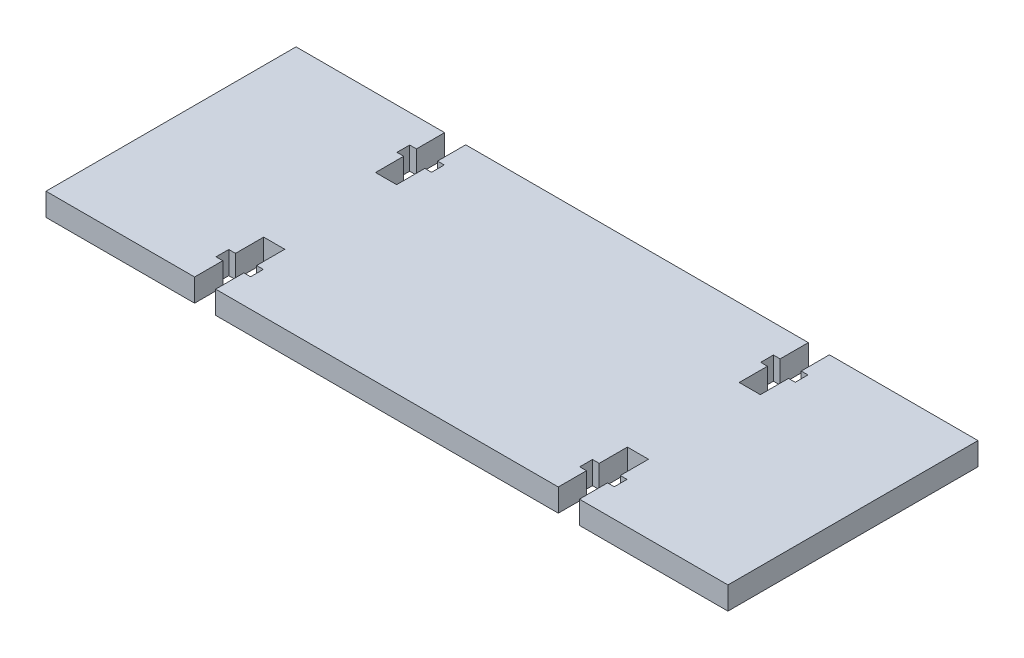
SolidWorks part; units mm, degrees
ref_plane "Front Plane" through (0, 0, 0) normal (0, 0, 1) x (1, 0, 0)
ref_plane "Top Plane" through (0, 0, 0) normal (0, 1, 0) x (1, 0, 0)
ref_plane "Right Plane" through (0, 0, 0) normal (1, 0, 0) x (0, 0, -1)
sketch "Sketch1" plane through (0, 0, 0) normal (0, 1, 0) x (1, 0, 0)
  line L1 (-47.625, -17.4625) -> (47.625, -17.4625)
  line L2 (-47.625, -17.4625) -> (-47.625, 17.4625)
  line L3 (-47.625, 17.4625) -> (47.625, 17.4625)
  line L4 (47.625, -17.4625) -> (47.625, 17.4625)
  line L5 (-47.625, -17.4625) -> (47.625, 17.4625) construction
  line L6 (-47.625, 17.4625) -> (47.625, -17.4625) construction
  point P0 (0, 0)
  dimension "D1" = 95.25
  dimension "D2" = 34.925
extrude "Boss-Extrude1" add sketch "Sketch1" along normal blind 3.175
sketch "Sketch2" plane through (0, 3.175, 0) normal (0, 1, 0) x (1, 0, 0)
  line L0 (-47.625, 17.4625) -> (-47.625, -17.4625) construction
  line L1 (-47.625, 9.4107) -> (-43.688, 9.4107)
  line L2 (-47.625, 9.4107) -> (-47.625, 6.4643)
  line L3 (-47.625, 6.4643) -> (-43.688, 6.4643)
  line L4 (-37.973, 9.4107) -> (-37.973, 6.4643)
  line L5 (-47.625, 9.4107) -> (-37.973, 6.4643) construction
  line L6 (-47.625, 7.9375) -> (-37.973, 7.9375) construction
  line L7 (47.625, 17.4625) -> (-47.625, 17.4625) construction
  line L8 (0, 0) -> (0, 17.4625) construction
  line L9 (-43.688, 5.5245) -> (-41.91, 5.5245)
  line L10 (-43.688, 5.5245) -> (-43.688, 6.4643)
  line L11 (-43.688, 10.3505) -> (-41.91, 10.3505)
  line L12 (-41.91, 5.5245) -> (-41.91, 6.4643)
  line L13 (-43.688, 5.5245) -> (-41.91, 10.3505) construction
  line L14 (-43.688, 10.3505) -> (-41.91, 5.5245) construction
  line L15 (-43.688, 9.4107) -> (-43.688, 10.3505)
  line L16 (-41.91, 6.4643) -> (-37.973, 6.4643)
  line L17 (-41.91, 9.4107) -> (-41.91, 10.3505)
  line L18 (-41.91, 9.4107) -> (-37.973, 9.4107)
  line L19 (-47.625, -6.4643) -> (-43.688, -6.4643)
  line L20 (-47.625, -6.4643) -> (-47.625, -9.4107)
  line L21 (-47.625, -9.4107) -> (-43.688, -9.4107)
  line L22 (-37.973, -6.4643) -> (-37.973, -9.4107)
  line L23 (-43.688, -10.3505) -> (-41.91, -10.3505)
  line L24 (-43.688, -10.3505) -> (-43.688, -9.4107)
  line L25 (-43.688, -5.5245) -> (-41.91, -5.5245)
  line L26 (-41.91, -10.3505) -> (-41.91, -9.4107)
  line L27 (-43.688, -6.4643) -> (-43.688, -5.5245)
  line L28 (-41.91, -9.4107) -> (-37.973, -9.4107)
  line L29 (-41.91, -6.4643) -> (-41.91, -5.5245)
  line L30 (-41.91, -6.4643) -> (-37.973, -6.4643)
  line L31 (-47.625, -6.4643) -> (-37.973, -9.4107) construction
  line L32 (-47.625, -7.9375) -> (-37.973, -7.9375) construction
  line L33 (-43.688, -10.3505) -> (-41.91, -5.5245) construction
  line L34 (-43.688, -5.5245) -> (-41.91, -10.3505) construction
  line L35 (43.688, -5.5245) -> (41.91, -10.3505) construction
  line L36 (43.688, -10.3505) -> (41.91, -5.5245) construction
  line L37 (47.625, -7.9375) -> (37.973, -7.9375) construction
  line L38 (47.625, -6.4643) -> (37.973, -9.4107) construction
  line L39 (43.688, 10.3505) -> (41.91, 5.5245) construction
  line L40 (43.688, 5.5245) -> (41.91, 10.3505) construction
  line L41 (47.625, 7.9375) -> (37.973, 7.9375) construction
  line L42 (47.625, 9.4107) -> (37.973, 6.4643) construction
  line L43 (41.91, -6.4643) -> (37.973, -6.4643)
  line L44 (41.91, -6.4643) -> (41.91, -5.5245)
  line L45 (41.91, -9.4107) -> (37.973, -9.4107)
  line L46 (43.688, -6.4643) -> (43.688, -5.5245)
  line L47 (41.91, -10.3505) -> (41.91, -9.4107)
  line L48 (43.688, -5.5245) -> (41.91, -5.5245)
  line L49 (43.688, -10.3505) -> (43.688, -9.4107)
  line L50 (43.688, -10.3505) -> (41.91, -10.3505)
  line L51 (37.973, -6.4643) -> (37.973, -9.4107)
  line L52 (47.625, -9.4107) -> (43.688, -9.4107)
  line L53 (47.625, -6.4643) -> (47.625, -9.4107)
  line L54 (47.625, -6.4643) -> (43.688, -6.4643)
  line L55 (41.91, 9.4107) -> (37.973, 9.4107)
  line L56 (41.91, 9.4107) -> (41.91, 10.3505)
  line L57 (41.91, 6.4643) -> (37.973, 6.4643)
  line L58 (43.688, 9.4107) -> (43.688, 10.3505)
  line L59 (41.91, 5.5245) -> (41.91, 6.4643)
  line L60 (43.688, 10.3505) -> (41.91, 10.3505)
  line L61 (43.688, 5.5245) -> (43.688, 6.4643)
  line L62 (43.688, 5.5245) -> (41.91, 5.5245)
  line L63 (37.973, 9.4107) -> (37.973, 6.4643)
  line L64 (47.625, 6.4643) -> (43.688, 6.4643)
  line L65 (47.625, 9.4107) -> (47.625, 6.4643)
  line L66 (47.625, 9.4107) -> (43.688, 9.4107)
  point P10 (-42.799, 7.9375)
  point P30 (-42.799, -7.9375)
  point P65 (42.799, -7.9375)
  point P66 (42.799, 7.9375)
  dimension "D1" = 9.525
  dimension "D2" = 2.9464
  dimension "D3" = 9.652
  dimension "D4" = 1.778
  dimension "D5" = 4.826
  dimension "D6" = 2
extrude "Cut-Extrude1" [suppressed] cut sketch "Sketch2" against normal through all
sketch "Sketch3" plane through (0, 3.175, 0) normal (0, 1, 0) x (1, 0, 0)
  line L0 (47.625, 17.4625) -> (-47.625, 17.4625) construction
  line L1 (-26.8732, 17.4625) -> (-23.9268, 17.4625)
  line L2 (-26.8732, 17.4625) -> (-26.8732, 13.5255)
  line L3 (-26.8732, 7.8105) -> (-23.9268, 7.8105)
  line L4 (-23.9268, 17.4625) -> (-23.9268, 13.5255)
  line L5 (-26.8732, 17.4625) -> (-23.9268, 7.8105) construction
  line L6 (-25.4, 17.4625) -> (-25.4, 7.8105) construction
  line L7 (0, -17.4625) -> (0, 17.4625) construction
  line L8 (-22.987, 13.5255) -> (-23.9268, 13.5255)
  line L9 (-22.987, 13.5255) -> (-22.987, 11.7475)
  line L10 (-22.987, 11.7475) -> (-23.9268, 11.7475)
  line L11 (-27.813, 13.5255) -> (-27.813, 11.7475)
  line L12 (-22.987, 13.5255) -> (-27.813, 11.7475) construction
  line L13 (-22.987, 11.7475) -> (-27.813, 13.5255) construction
  line L14 (0, 0) -> (-47.625, 0) construction
  line L15 (-47.625, 17.4625) -> (-47.625, -17.4625) construction
  line L16 (-26.8732, 13.5255) -> (-27.813, 13.5255)
  line L17 (-26.8732, 11.7475) -> (-26.8732, 7.8105)
  line L18 (-26.8732, 11.7475) -> (-27.813, 11.7475)
  line L19 (-23.9268, 11.7475) -> (-23.9268, 7.8105)
  line L20 (23.9268, 17.4625) -> (26.8732, 17.4625)
  line L21 (23.9268, 17.4625) -> (23.9268, 13.5255)
  line L22 (23.9268, 7.8105) -> (26.8732, 7.8105)
  line L23 (26.8732, 17.4625) -> (26.8732, 13.5255)
  line L24 (27.813, 13.5255) -> (26.8732, 13.5255)
  line L25 (27.813, 13.5255) -> (27.813, 11.7475)
  line L26 (27.813, 11.7475) -> (26.8732, 11.7475)
  line L27 (22.987, 13.5255) -> (22.987, 11.7475)
  line L28 (23.9268, 13.5255) -> (22.987, 13.5255)
  line L29 (23.9268, 11.7475) -> (23.9268, 7.8105)
  line L30 (23.9268, 11.7475) -> (22.987, 11.7475)
  line L31 (26.8732, 11.7475) -> (26.8732, 7.8105)
  line L32 (23.9268, 17.4625) -> (26.8732, 7.8105) construction
  line L33 (25.4, 17.4625) -> (25.4, 7.8105) construction
  line L34 (27.813, 13.5255) -> (22.987, 11.7475) construction
  line L35 (27.813, 11.7475) -> (22.987, 13.5255) construction
  line L36 (27.813, -11.7475) -> (22.987, -13.5255) construction
  line L37 (27.813, -13.5255) -> (22.987, -11.7475) construction
  line L38 (25.4, -17.4625) -> (25.4, -7.8105) construction
  line L39 (23.9268, -17.4625) -> (26.8732, -7.8105) construction
  line L40 (-22.987, -11.7475) -> (-27.813, -13.5255) construction
  line L41 (-22.987, -13.5255) -> (-27.813, -11.7475) construction
  line L42 (-25.4, -17.4625) -> (-25.4, -7.8105) construction
  line L43 (-26.8732, -17.4625) -> (-23.9268, -7.8105) construction
  line L44 (26.8732, -11.7475) -> (26.8732, -7.8105)
  line L45 (23.9268, -11.7475) -> (22.987, -11.7475)
  line L46 (23.9268, -11.7475) -> (23.9268, -7.8105)
  line L47 (23.9268, -13.5255) -> (22.987, -13.5255)
  line L48 (22.987, -13.5255) -> (22.987, -11.7475)
  line L49 (27.813, -11.7475) -> (26.8732, -11.7475)
  line L50 (27.813, -13.5255) -> (27.813, -11.7475)
  line L51 (27.813, -13.5255) -> (26.8732, -13.5255)
  line L52 (26.8732, -17.4625) -> (26.8732, -13.5255)
  line L53 (23.9268, -7.8105) -> (26.8732, -7.8105)
  line L54 (23.9268, -17.4625) -> (23.9268, -13.5255)
  line L55 (23.9268, -17.4625) -> (26.8732, -17.4625)
  line L56 (-23.9268, -11.7475) -> (-23.9268, -7.8105)
  line L57 (-26.8732, -11.7475) -> (-27.813, -11.7475)
  line L58 (-26.8732, -11.7475) -> (-26.8732, -7.8105)
  line L59 (-26.8732, -13.5255) -> (-27.813, -13.5255)
  line L60 (-27.813, -13.5255) -> (-27.813, -11.7475)
  line L61 (-22.987, -11.7475) -> (-23.9268, -11.7475)
  line L62 (-22.987, -13.5255) -> (-22.987, -11.7475)
  line L63 (-22.987, -13.5255) -> (-23.9268, -13.5255)
  line L64 (-23.9268, -17.4625) -> (-23.9268, -13.5255)
  line L65 (-26.8732, -7.8105) -> (-23.9268, -7.8105)
  line L66 (-26.8732, -17.4625) -> (-26.8732, -13.5255)
  line L67 (-26.8732, -17.4625) -> (-23.9268, -17.4625)
  line L68 (47.625, -17.4625) -> (47.625, 17.4625) construction
  point P8 (-25.4, 12.6365)
  point P31 (25.4, 12.6365)
  point P67 (25.4, -12.6365)
  point P68 (-25.4, -12.6365)
  dimension "D1" = 9.652
  dimension "D2" = 2.9464
  dimension "D3" = 1.778
  dimension "D4" = 4.826
  dimension "D5" = 25.4
  dimension "D6" = 2
extrude "Cut-Extrude2" cut sketch "Sketch3" against normal through all
